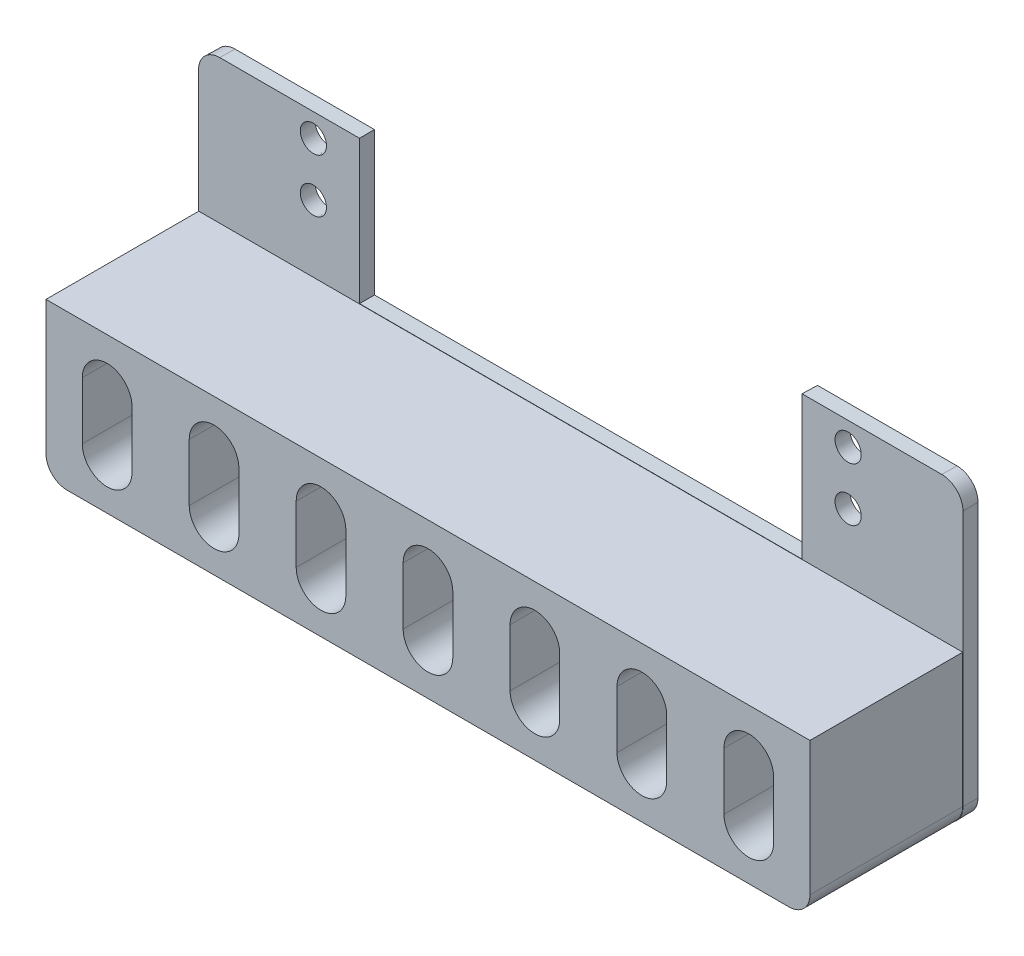
SolidWorks part; units mm, degrees
ref_plane "前视基准面" through (0, 0, 0) normal (0, 0, 1) x (1, 0, 0)
ref_plane "上视基准面" through (0, 0, 0) normal (0, 1, 0) x (1, 0, 0)
ref_plane "右视基准面" through (0, 0, 0) normal (1, 0, 0) x (0, 0, -1)
sketch "草图1" plane through (0, 0, 0) normal (0, 0, 1) x (1, 0, 0)
  line L0 (50, 6.25) -> (50, 13.75) construction
  line L1 (2.7446, 0) -> (97.2554, 0)
  line L2 (0, 2.7446) -> (0, 36.2554)
  line L3 (2.7446, 39) -> (21, 39)
  line L4 (100, 2.7446) -> (100, 36.2554)
  line L5 (0, 0) -> (100, 39) construction
  line L6 (0, 39) -> (100, 0) construction
  line L7 (46.75, 6.25) -> (46.75, 13.75)
  line L8 (53.25, 6.25) -> (53.25, 13.75)
  line L9 (36, 6.25) -> (36, 13.75) construction
  line L10 (32.75, 6.25) -> (32.75, 13.75)
  line L11 (39.25, 6.25) -> (39.25, 13.75)
  line L12 (64, 6.25) -> (64, 13.75) construction
  line L13 (60.75, 6.25) -> (60.75, 13.75)
  line L14 (67.25, 6.25) -> (67.25, 13.75)
  line L15 (78, 6.25) -> (78, 13.75) construction
  line L16 (74.75, 6.25) -> (74.75, 13.75)
  line L17 (81.25, 6.25) -> (81.25, 13.75)
  line L18 (92, 6.25) -> (92, 13.75) construction
  line L19 (88.75, 6.25) -> (88.75, 13.75)
  line L20 (95.25, 6.25) -> (95.25, 13.75)
  line L21 (22, 6.25) -> (22, 13.75) construction
  line L22 (18.75, 6.25) -> (18.75, 13.75)
  line L23 (25.25, 6.25) -> (25.25, 13.75)
  line L24 (8, 6.25) -> (8, 13.75) construction
  line L25 (4.75, 6.25) -> (4.75, 13.75)
  line L26 (11.25, 6.25) -> (11.25, 13.75)
  line L27 (0, 20.25) -> (100, 20.25)
  line L28 (0, 33) -> (21, 33)
  line L29 (21, 39) -> (21, 20.25)
  line L30 (79, 20.25) -> (79, 39)
  line L31 (79, 39) -> (97.2554, 39)
  line L32 (79, 33) -> (100, 33)
  arc A0 (46.75, 6.25) -> (53.25, 6.25) centre (50, 6.25) ccw
  arc A1 (53.25, 13.75) -> (46.75, 13.75) centre (50, 13.75) ccw
  arc A2 (32.75, 6.25) -> (39.25, 6.25) centre (36, 6.25) ccw
  arc A3 (39.25, 13.75) -> (32.75, 13.75) centre (36, 13.75) ccw
  arc A4 (60.75, 6.25) -> (67.25, 6.25) centre (64, 6.25) ccw
  arc A5 (67.25, 13.75) -> (60.75, 13.75) centre (64, 13.75) ccw
  arc A6 (74.75, 6.25) -> (81.25, 6.25) centre (78, 6.25) ccw
  arc A7 (81.25, 13.75) -> (74.75, 13.75) centre (78, 13.75) ccw
  arc A8 (88.75, 6.25) -> (95.25, 6.25) centre (92, 6.25) ccw
  arc A9 (95.25, 13.75) -> (88.75, 13.75) centre (92, 13.75) ccw
  arc A10 (18.75, 6.25) -> (25.25, 6.25) centre (22, 6.25) ccw
  arc A11 (25.25, 13.75) -> (18.75, 13.75) centre (22, 13.75) ccw
  arc A12 (4.75, 6.25) -> (11.25, 6.25) centre (8, 6.25) ccw
  arc A13 (11.25, 13.75) -> (4.75, 13.75) centre (8, 13.75) ccw
  circle A14 centre (15, 29) radius 1.75
  circle A15 centre (85, 29) radius 1.75
  circle A16 centre (15, 36) radius 1.75
  circle A17 centre (85, 36) radius 1.75
  arc A18 (97.2554, 0) -> (100, 2.7446) centre (97.2554, 2.7446) ccw
  arc A19 (100, 36.2554) -> (97.2554, 39) centre (97.2554, 36.2554) ccw
  arc A20 (0, 2.7446) -> (2.7446, 0) centre (2.7446, 2.7446) ccw
  arc A21 (0, 36.2554) -> (2.7446, 39) centre (2.7446, 36.2554) cw
  point P0 (50, 19.5)
  point P8 (50, 10)
  point P17 (36, 10)
  point P24 (64, 10)
  point P31 (78, 10)
  point P38 (92, 10)
  point P45 (22, 10)
  point P52 (8, 10)
  point P67 (15.1398, 29.2125)
  point P70 (82.2715, 30.2866)
  point P73 (15, 36.0222)
  point P76 (85, 36.0222)
  point P77 (0, 0)
  point P78 (0, 0)
  point P79 (0, 0)
  point P80 (0, 0)
  point P81 (0, 0)
  point P82 (0, 0)
  point P83 (0, 0)
  dimension "D21" = 7.5
  dimension "D35" = 29
  dimension "D37" = 3.5
  dimension "D40" = 3.5
  dimension "D43" = 3.5
  dimension "D44" = 3.5
  dimension "D49" = 2.7446
  dimension "D1" = 100
  dimension "D2" = 39
  dimension "D3" = 3.25
  dimension "D4" = 7.5
  dimension "D5" = 6.25
  dimension "D6" = 50
  dimension "D7" = 0
  dimension "D8" = 0
  dimension "D9" = 6.25
  dimension "D10" = 7.5
  dimension "D11" = 3.25
  dimension "D12" = 3.25
  dimension "D13" = 7.5
  dimension "D14" = 6.25
  dimension "D15" = 7.5
  dimension "D16" = 7.5
  dimension "D17" = 7.5
  dimension "D18" = 3.25
  dimension "D19" = 6.25
  dimension "D20" = 7.5
  dimension "D22" = 6.25
  dimension "D23" = 7.5
  dimension "D24" = 3.25
  dimension "D25" = 6.25
  dimension "D26" = 7.5
  dimension "D27" = 7.5
  dimension "D28" = 3.25
  dimension "D29" = 7.5
  dimension "D30" = 3.25
  dimension "D31" = 6.25
  dimension "D32" = 7.5
  dimension "D33" = 6.5
  dimension "D34" = 33
  dimension "D36" = 29
  dimension "D38" = 4
  dimension "D39" = 35
  dimension "D41" = 4
  dimension "D42" = 35
  dimension "D45" = 35
  dimension "D46" = 35
  dimension "D47" = 3
  dimension "D48" = 3
extrude "凸台-拉伸3" add sketch "草图1" along normal blind 2 draft 1 contours L29 L3 L2 L28 A16 | L29 L28 L2 L27 A14 | L27 L2 L1 L4 A13 L26 A12 L25 A11 L23 A10 L22 A9 L20 A8 L19 A7 L17 A6 L16 A5 L14 A4 L13 A3 L11 A2 L10 A1 L8 A0 L7 | L32 L30 L27 L4 A15 | L30 L32 L4 L31 A17 region at (1.5253, 1.5253, 0) region at (10.3323, 26.5365, 0) region at (89.6677, 26.5365, 0) region at (10.262, 35.9664, 0) region at (89.738, 35.9664, 0) draft outward yes
extrude "凸台-拉伸4" add sketch "草图1<8>" along normal blind 22 contours L27 L2 L1 L4 A13 L26 A12 L25 A11 L23 A10 L22 A9 L20 A8 L19 A7 L17 A6 L16 A5 L14 A4 L13 A3 L11 A2 L10 A1 L8 A0 L7 region at (1.5253, 1.5253, 0)
sketch "草图1<8>" plane through (0, 0, 0) normal (0, 0, 1) x (1, 0, 0) same geometry as "草图1"
